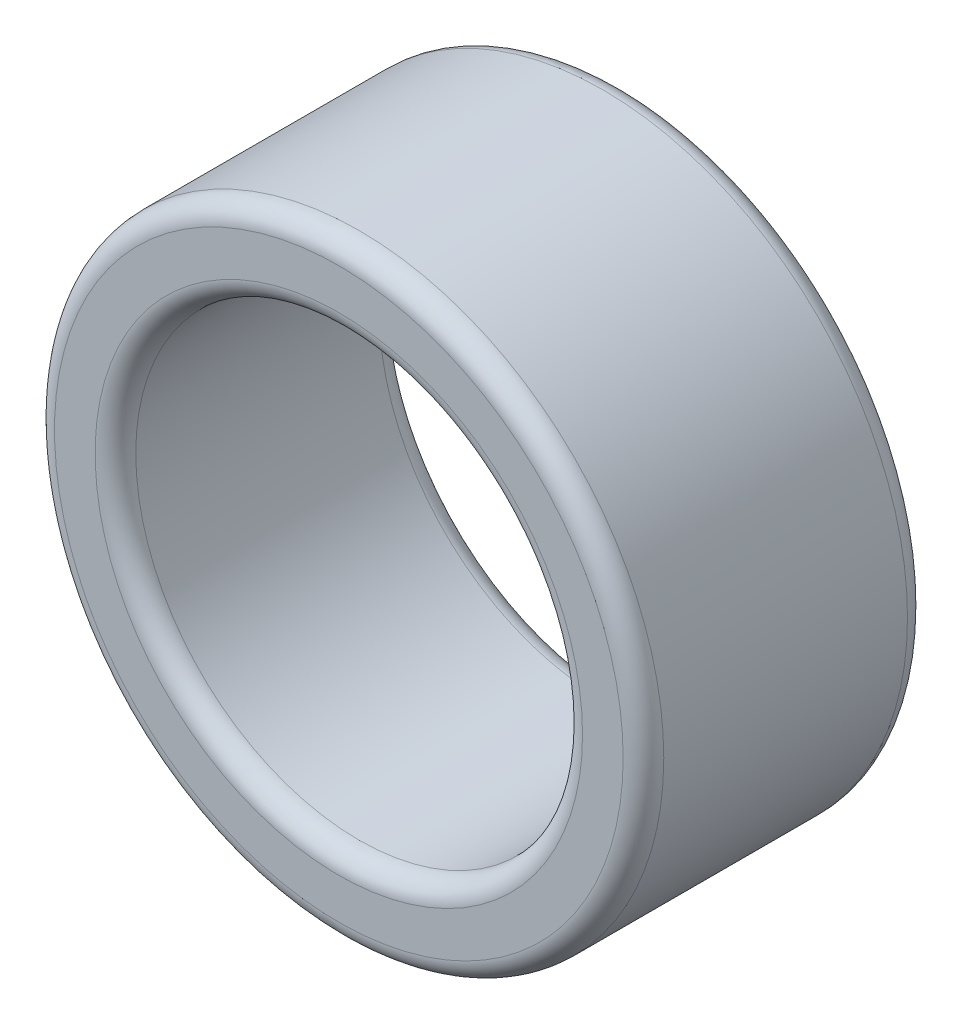
SolidWorks part; units mm, degrees
material "Silicon Rubber"
ref_plane "Front Plane" through (0, 0, 0) normal (0, 0, 1) x (1, 0, 0)
ref_plane "Top Plane" through (0, 0, 0) normal (0, 1, 0) x (1, 0, 0)
ref_plane "Right Plane" through (0, 0, 0) normal (1, 0, 0) x (0, 0, -1)
sketch "Sketch2" plane through (0, 0, 0) normal (0, 0, 1) x (1, 0, 0)
  circle A0 centre (0, 0) radius 381
  dimension "D1" = 762
extrude "Boss-Extrude1" add sketch "Sketch2" along normal blind 355.6
sketch "Sketch3" plane through (0, 0, 355.6) normal (0, 0, 1) x (1, 0, 0)
  circle A0 centre (0, 0) radius 279.4
  dimension "D1" = 558.8
extrude "Cut-Extrude1" cut sketch "Sketch3" against normal through all
fillet "Fillet3" radius 25.4 2 edges at (381, 0, 0) (381, 0, 355.6)
fillet "Fillet4" radius 25.4 2 edges at (279.4, 0, 0) (279.4, 0, 355.6)
